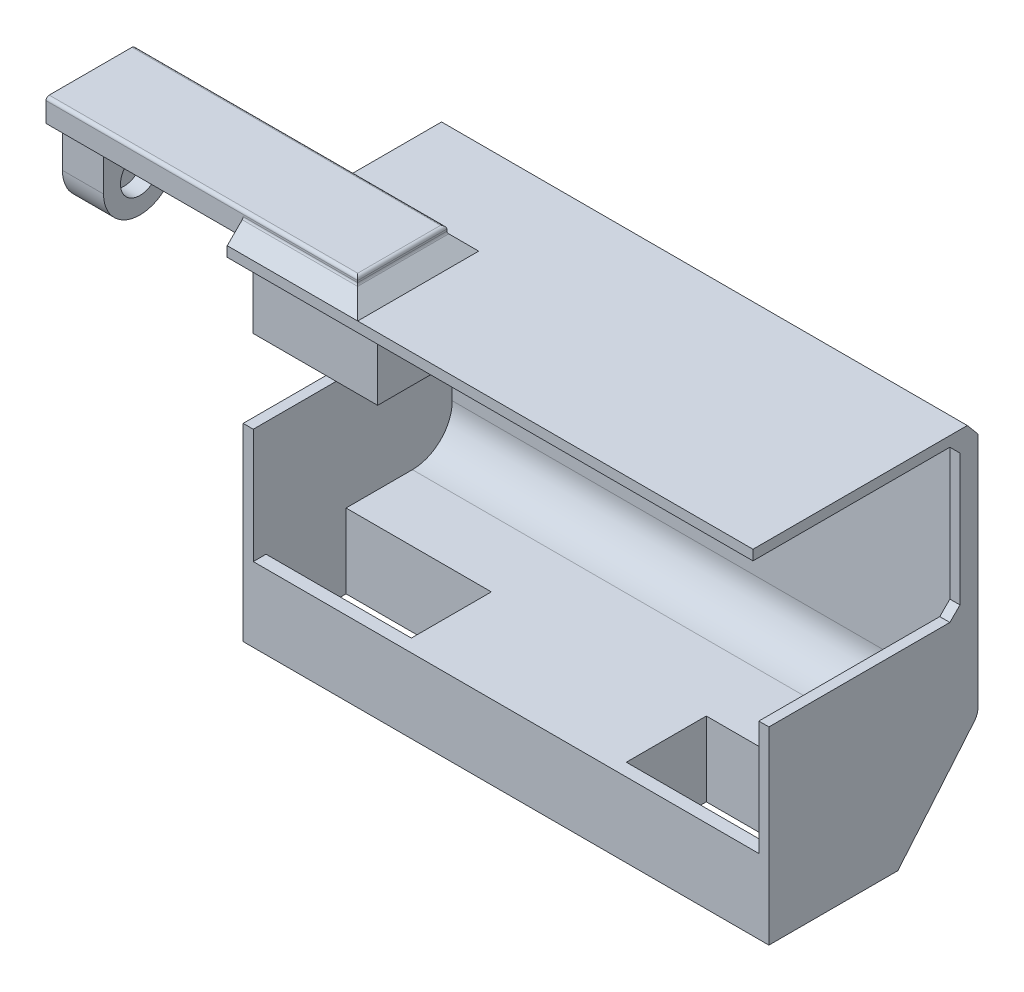
SolidWorks part; units mm, degrees
material "PLA"
ref_plane "Front Plane" through (0, 0, 0) normal (0, 0, 1) x (1, 0, 0)
ref_plane "Top Plane" through (0, 0, 0) normal (0, 1, 0) x (1, 0, 0)
ref_plane "Right Plane" through (0, 0, 0) normal (1, 0, 0) x (0, 0, -1)
sketch "Sketch1" plane through (0, 0, 0) normal (0, 1, 0) x (1, 0, 0)
  line L0 (0, -25.4) -> (0, 28.6) construction
  line L1 (-82.55, -25.4) -> (82.55, -25.4)
  line L2 (-82.55, -25.4) -> (-82.55, 28.6)
  line L3 (-82.55, 28.6) -> (82.55, 28.6)
  line L4 (82.55, -25.4) -> (82.55, 28.6)
  line L5 (-82.55, 1.6) -> (82.55, 1.6) construction
  point P4 (0, -25.4)
  point P5 (-82.55, 1.6)
  point P8 (0, 0)
  point P12 (0, 0)
  dimension "D1" = 165.1
  dimension "D2" = 54
extrude "Boss-Extrude1" add sketch "Sketch1" along normal blind 6.35
sketch "Sketch6" plane through (-82.55, 0, 0) normal (-1, 0, 0) x (0, 0, 1)
  line L1 (-37.0827, 90) -> (-37.0827, 6.35)
  line L4 (-40.2577, 90) -> (-37.0827, 90)
  line L7 (-28.6, 6.35) -> (-28.6, 0)
  line L8 (-28.6, 6.35) -> (-37.0827, 6.35)
  line L9 (-28.6, 0) -> (-40.2577, 0)
  line L10 (-40.2577, 0) -> (-40.2577, 90)
  dimension "D4" = 3.175
extrude "Boss-Extrude2" add sketch "Sketch6" against normal up to surface (165.1 mm away) up to face at (82.55, 3.175, -1.6)
sketch "Sketch7" plane through (0, 0, 25.4) normal (0, 0, 1) x (1, 0, 0)
  line L0 (-82.55, 0) -> (82.55, 0) construction
  line L1 (-82.55, 90) -> (-79.375, 90)
  line L2 (-82.55, 90) -> (-82.55, 0)
  line L3 (-82.55, 0) -> (-79.375, 0)
  line L4 (-79.375, 90) -> (-79.375, 0)
  line L6 (82.55, 0) -> (79.375, 0)
  line L7 (82.55, 0) -> (82.55, 90)
  line L8 (82.55, 90) -> (79.375, 90)
  line L9 (79.375, 0) -> (79.375, 90)
  dimension "D1" = 3.175
  dimension "D2" = 3.175
extrude "Boss-Extrude3" add sketch "Sketch7" against normal up to surface (62.4827 mm away) up to face at (0, 48.175, -37.0827)
sketch "Sketch9" plane through (0, 0, -40.2577) normal (0, 0, -1) x (-1, 0, 0)
  line L0 (-82.55, 0) -> (-82.55, 90) construction
  line L5 (82.55, 90) -> (82.55, 0) construction
  line L6 (-82.55, 0) -> (82.55, 0) construction
  line L7 (-82.55, 90) -> (82.55, 90) construction
  line L8 (-65.55, 83) -> (65.55, 83)
  line L9 (-67.55, 81) -> (-67.55, 32)
  line L10 (-65.55, 30) -> (65.55, 30)
  line L16 (67.55, 81) -> (67.55, 32)
  arc A0 (-67.55, 32) -> (-65.55, 30) centre (-65.55, 32) ccw
  arc A1 (65.55, 30) -> (67.55, 32) centre (65.55, 32) ccw
  arc A2 (65.55, 83) -> (67.55, 81) centre (65.55, 81) cw
  arc A3 (-65.55, 83) -> (-67.55, 81) centre (-65.55, 81) ccw
  dimension "D5" = 2
  dimension "D1" = 7
  dimension "D2" = 15
  dimension "D3" = 15
  dimension "D4" = 30
extrude "Boss-Extrude4" add sketch "Sketch9" along normal blind 1
sketch "Sketch10" plane through (-82.55, 0, 0) normal (-1, 0, 0) x (0, 0, 1)
  line L0 (25.4, 0) -> (25.4, 42.35) construction
  line L1 (25.4, 90) -> (25.4, 0) construction
  line L2 (25.4, 42.35) -> (-34.6, 42.35)
  line L3 (-34.6, 42.35) -> (-34.6, 90)
  line L5 (-34.6, 90) -> (25.4, 90)
  line L6 (25.4, 90) -> (25.4, 42.35)
  dimension "D1" = 42.35
  dimension "D2" = 60
extrude "Cut-Extrude2" cut sketch "Sketch10" against normal through all both and the other way through all
sketch "Sketch12" plane through (0, 90, 0) normal (0, 1, 0) x (1, 0, 0)
  line L3 (-82.55, -25.4) -> (-82.55, -30.4)
  line L4 (-82.55, 40.2577) -> (82.55, 40.2577)
  line L5 (82.55, 40.2577) -> (82.55, -25.4)
  line L7 (-82.55, -25.4) -> (-82.55, 40.2577)
  line L8 (-82.55, -30.4) -> (82.55, -30.4)
  line L9 (82.55, -30.4) -> (82.55, -25.4)
  dimension "D1" = 5
extrude "Boss-Extrude6" add sketch "Sketch12" along normal blind 3.175
sketch "Sketch15" plane through (0, 0, 0) normal (0, -1, 0) x (1, 0, 0)
  line L0 (82.55, 33.9) -> (82.55, -40.2577) construction
  line L1 (82.55, -3.1788) -> (-82.55, -3.1788) construction
  line L2 (-82.55, -40.2577) -> (-82.55, 25.4) construction
  line L3 (-82.55, 25.4) -> (82.55, 25.4) construction
  line L4 (-82.55, -3.1788) -> (-82.55, 8.8212) construction
  line L5 (-82.55, 8.8212) -> (82.55, 8.8212) construction
  line L6 (0, -3.1788) -> (0, 32.5085) construction
  line B0 (-66.875, 21.3812) -> (-66.875, 8.8212) construction
  line B1 (-33.755, 21.3812) -> (-79.375, 21.3812) construction
  line B2 (-33.755, -3.7388) -> (-79.375, -3.7388) construction
  line B3 (-33.755, 21.3812) -> (-33.755, -3.7388) construction
  line B4 (-79.375, -3.7388) -> (-79.375, 21.3812) construction
  line B5 (-46.255, 21.3812) -> (-46.255, 8.8212) construction
  line B6 (-79.375, -3.7388) -> (-33.755, -3.7388)
  line B7 (-79.375, -3.7388) -> (-79.375, 21.3812)
  line B8 (-79.375, 21.3812) -> (-33.755, 21.3812)
  line B9 (-33.755, -3.7388) -> (-33.755, 21.3812)
  circle B10 centre (-46.255, 8.8212) radius 3 construction
  line B11 (79.375, 21.3812) -> (33.755, 21.3812) construction
  line B12 (66.875, 21.3812) -> (66.875, 8.8212) construction
  line B13 (79.375, -3.7388) -> (33.755, -3.7388) construction
  line B14 (79.375, 21.3812) -> (79.375, -3.7388) construction
  line B15 (46.255, 21.3812) -> (46.255, 8.8212) construction
  line B16 (33.755, -3.7388) -> (33.755, 21.3812) construction
  line B17 (33.755, -3.7388) -> (79.375, -3.7388)
  line B18 (33.755, -3.7388) -> (33.755, 21.3812)
  line B19 (33.755, 21.3812) -> (79.375, 21.3812)
  line B20 (79.375, -3.7388) -> (79.375, 21.3812)
  circle B21 centre (46.255, 8.8212) radius 3 construction
  dimension "D1" = 3.175
  dimension "D2" = 3.175
  dimension "D3" = 12
sketch_block_instance "Block1-1"
sketch_block "Block1" parameters "D4"=6, "D1"=25.12, "D2"=45.62, "D3"=12.5, "D5"=12.5
sketch_block_instance "Block2-1"
sketch_block "Block2" parameters "D4"=6, "D1"=45.62, "D2"=12.5, "D3"=25.12, "D5"=12.5
extrude "Cut-Extrude3" cut sketch "Sketch15" against normal blind 10
sketch "Sketch16" plane through (0, 0, 0) normal (0, -1, 0) x (1, 0, 0)
  line L0 (33.755, -3.7388) -> (79.375, -3.7388) construction
  line L1 (-79.375, -3.7388) -> (-33.755, -3.7388)
  line L2 (-79.375, -3.7388) -> (-79.375, 21.3812)
  line L3 (-79.375, 21.3812) -> (-33.755, 21.3812)
  line L4 (82.55, -40.2577) -> (82.55, 25.4)
  line L5 (82.55, 25.4) -> (-82.55, 25.4)
  line L6 (-82.55, 25.4) -> (-82.55, -40.2577)
  line L7 (-82.55, -40.2577) -> (82.55, -40.2577)
  line L8 (82.55, -40.2577) -> (82.55, 25.4)
  line L9 (82.55, 25.4) -> (-82.55, 25.4)
  line L10 (-82.55, 25.4) -> (-82.55, -40.2577)
  line L11 (-82.55, -40.2577) -> (82.55, -40.2577)
  line L12 (-33.755, -3.7388) -> (-33.755, 21.3812)
  line L14 (33.755, 21.3812) -> (33.755, -3.7388)
  line L17 (79.375, -3.7388) -> (79.375, 21.3812) construction
  line L18 (79.375, 21.3812) -> (33.755, 21.3812) construction
  line L19 (33.755, -3.7388) -> (79.375, -3.7388)
  line L20 (79.375, -3.7388) -> (79.375, 21.3812)
  line L21 (79.375, 21.3812) -> (33.755, 21.3812)
  dimension "D1" = 0
extrude "Boss-Extrude7" add sketch "Sketch16" along normal blind 17
chamfer "Chamfer2" distance 4 angle 40 1 edges at (0, 93.175, -40.2577) first distance on face at (0, 56.5, -40.2577)
chamfer "Chamfer3" distance 30 angle 40 1 edges at (0, -17, -40.2577) first distance on face at (0, 56.5, -40.2577)
fillet "Fillet1" radius 12.5 1 edges at (0, 6.35, -37.0827)
fillet "Fillet2" radius 5 1 edges at (0, 13, -40.2577)
chamfer "Chamfer5" distance 3.175 angle 45 2 edges at (-80.9625, 90, -34.6) (80.9625, 90, -34.6)
chamfer "Chamfer6" distance 3.175 angle 45 2 edges at (80.9625, 42.35, -34.6) (-80.9625, 42.35, -34.6)
sketch "Sketch18" plane through (0, 93.175, 0) normal (0, 1, 0) x (1, 0, 0)
  line L0 (-82.8, 26.2862) -> (-82.8, 26.4862) construction
  line L1 (-83.35, 26.2862) -> (-82.25, 26.2862) construction
  line L2 (-82.55, 36.9013) -> (-82.55, -30.4) construction
  line L3 (-82.55, 36.9013) -> (-82.55, -30.4) construction
  line L4 (-82.8, 26.4862) -> (-46.5819, 26.4862) construction
  line L5 (-46.5819, 26.4862) -> (-46.5819, -19.9043) construction
  line L6 (-80.85, -18.9297) -> (-80.85, -19.1297) construction
  line L7 (-82.55, -19.1297) -> (-46.5819, -19.1297)
  line L8 (-46.5819, -19.1297) -> (-46.5819, 26.4862)
  line L9 (-80.85, -18.9297) -> (-74.95, -18.9297)
  line L10 (-74.95, -18.9297) -> (-74.95, -18.2883)
  line L11 (-74.95, -18.2883) -> (-80.85, -18.2883)
  line L12 (-80.85, -18.9297) -> (-74.95, -18.9297)
  line L13 (-46.5819, 26.4862) -> (-82.55, 26.4862)
  line L15 (-82.55, -22.3047) -> (-43.4069, -22.3047)
  line L16 (-43.4069, -22.3047) -> (-43.4069, 29.6612)
  line L17 (-43.4069, 29.6612) -> (-82.55, 29.6612)
  line L18 (-82.55, 29.6612) -> (-82.55, 26.4862)
  line L19 (-82.55, -22.3047) -> (-82.55, -19.1297)
  spline S1 degree 3 poles (-1054.8455, 208.2772) (893.5385, -208.2061) (-1055.3981, 170.5876) (893.6165, -243.4552) knots -0.027165 -0.027165 -0.027165 -0.027165 0.027597 0.027597 0.027597 0.027597 only from (-80.85, -18.2883) to (-80.85, -18.9297)
  dimension "D1" = 0.2
  dimension "D3" = 0.2
  dimension "D2" = 0
  dimension "D4" = 3.175
extrude "Boss-Extrude9" add sketch "Sketch18" against normal blind 27.895 contours L16 L17 L13 L8 L7 L15 region at (-64.5659, 93.175, 19.7803)
sketch "Sketch19" plane through (0, 93.175, 0) normal (0, 1, 0) x (1, 0, 0)
  line L3 (-46.5819, -25.4) -> (-82.55, -25.4)
  line L4 (-82.55, 36.9013) -> (-82.55, -30.4)
  line L5 (-82.55, -30.4) -> (82.55, -30.4)
  line L6 (82.55, -30.4) -> (82.55, 36.9013)
  line L7 (82.55, 36.9013) -> (-82.55, 36.9013)
  line L8 (-82.55, 36.9013) -> (-82.55, -30.4)
  line L9 (-82.55, -30.4) -> (82.55, -30.4)
  line L10 (82.55, -30.4) -> (82.55, 36.9013)
  line L11 (82.55, 36.9013) -> (-82.55, 36.9013)
  line L12 (-46.5819, 2.6) -> (-46.5819, -25.4)
  line L13 (-82.55, 2.6) -> (-46.5819, 2.6)
  line L14 (-82.55, 2.6) -> (-82.55, -25.4)
  dimension "D2" = 5
  dimension "D3" = 28
  dimension "D1" = 0
extrude "Boss-Extrude10" add sketch "Sketch19" along normal blind 5 contours L13 L8 L3 L12 region at (-64.5659, 93.175, 11.4)
chamfer "Chamfer11" distance 5 angle 45 3 edges at (-64.5659, 93.175, 25.4) (-46.5819, 93.175, 11.4) (-64.5659, 93.175, -2.6)
sketch "Sketch20" plane through (-82.55, 0, 0) normal (-1, 0, 0) x (0, 0, 1)
  line L10 (-2.6, 98.175) -> (25.4, 98.175)
  line L11 (25.4, 98.175) -> (25.4, 92.9612)
  line L12 (25.4, 92.9612) -> (-2.6, 92.9612)
  line L13 (-2.6, 92.9612) -> (-2.6, 98.175)
extrude "Boss-Extrude11" add sketch "Sketch20" along normal blind 53
sketch "Sketch21" plane through (-135.55, 0, 0) normal (-1, 0, 0) x (0, 0, 1)
  line L0 (8.82, 77.64) -> (8.82, 92.9612) construction
  line L1 (-2.6, 92.9612) -> (25.4, 92.9612) construction
  line L2 (8.82, 92.9612) -> (-2.6, 92.9612) construction
  line L3 (8.82, 92.9612) -> (20.24, 92.9612) construction
  line L4 (-2.6, 92.9612) -> (20.24, 92.9612)
  line L5 (20.24, 92.9612) -> (20.24, 77.64)
  line L6 (-2.6, 92.9612) -> (-2.6, 77.64)
  arc A0 (-2.6, 77.64) -> (20.24, 77.64) centre (8.82, 77.64) ccw
  circle A1 centre (8.82, 77.64) radius 6.1
  dimension "D2" = 12.2
  dimension "D1" = 11.42
extrude "Boss-Extrude12" add sketch "Sketch21" against normal blind 4
chamfer "Chamfer12" distance 5 angle 45 1 edges at (-133.55, 92.9612, 20.24)
sketch "Sketch22" plane through (-135.55, 0, 0) normal (-1, 0, 0) x (0, 0, 1)
  line L6 (-2.6, 98.175) -> (-2.6, 77.64)
  line L7 (20.24, 77.64) -> (20.24, 87.9612)
  line L8 (20.24, 87.9612) -> (25.24, 92.9612)
  line L9 (25.24, 92.9612) -> (25.4, 92.9612)
  line L10 (25.4, 92.9612) -> (25.4, 98.175)
  line L11 (25.4, 98.175) -> (-2.6, 98.175)
  line L12 (-2.6, 98.175) -> (-2.6, 77.64)
  line L13 (20.24, 77.64) -> (20.24, 87.9612)
  line L14 (20.24, 87.9612) -> (25.24, 92.9612)
  line L15 (25.24, 92.9612) -> (25.4, 92.9612)
  line L16 (25.4, 92.9612) -> (25.4, 98.175)
  line L17 (25.4, 98.175) -> (-2.6, 98.175)
  circle A0 centre (8.82, 77.64) radius 6.1 construction
  arc A1 (-2.6, 77.64) -> (20.24, 77.64) centre (8.82, 77.64) ccw
  arc A2 (-2.6, 77.64) -> (20.24, 77.64) centre (8.82, 77.64) ccw
  circle A3 centre (8.82, 77.64) radius 6.1
  dimension "D1" = 0
extrude "Boss-Extrude13" add sketch "Sketch22" along normal blind 1
sketch "Sketch23" plane through (-136.55, 0, 0) normal (-1, 0, 0) x (0, 0, 1)
  line L6 (25.4, 98.175) -> (-2.6, 98.175)
  line L7 (-2.6, 98.175) -> (-2.6, 77.64)
  line L8 (20.24, 77.64) -> (20.24, 87.9612)
  line L9 (20.24, 87.9612) -> (25.24, 92.9612)
  line L10 (25.24, 92.9612) -> (25.4, 92.9612)
  line L11 (25.4, 92.9612) -> (25.4, 98.175)
  line L12 (25.4, 98.175) -> (-2.6, 98.175)
  line L13 (-2.6, 98.175) -> (-2.6, 77.64)
  line L14 (20.24, 77.64) -> (20.24, 87.9612)
  line L15 (20.24, 87.9612) -> (25.24, 92.9612)
  line L16 (25.24, 92.9612) -> (25.4, 92.9612)
  line L17 (25.4, 92.9612) -> (25.4, 98.175)
  arc A1 (-2.6, 77.64) -> (20.24, 77.64) centre (8.82, 77.64) ccw
  arc A2 (-2.6, 77.64) -> (20.24, 77.64) centre (8.82, 77.64) ccw
  dimension "D1" = 0
extrude "Boss-Extrude14" add sketch "Sketch23" along normal blind 7.91
sketch "Sketch24" plane through (0, 98.175, 0) normal (0, 1, 0) x (1, 0, 0)
  line L1 (-46.5819, 2.6) -> (-144.46, 2.6)
  line L2 (-46.5819, 2.6) -> (-46.5819, -25.4)
  line L3 (-46.5819, -25.4) -> (-144.46, -25.4)
  line L4 (-144.46, 2.6) -> (-144.46, -25.4)
extrude "Boss-Extrude15" add sketch "Sketch24" along normal blind 2
fillet "Fillet3" radius 1 3 edges at (-95.5209, 100.175, 25.4) (-46.5819, 100.175, 11.4) (-95.5209, 100.175, -2.6)
fillet "Fillet4" radius 1 1 edges at (-64.5659, 98.175, -2.6)
fillet "Fillet5" radius 1 2 edges at (-64.5659, 98.175, 25.4) (-46.5819, 98.175, 11.3551)
